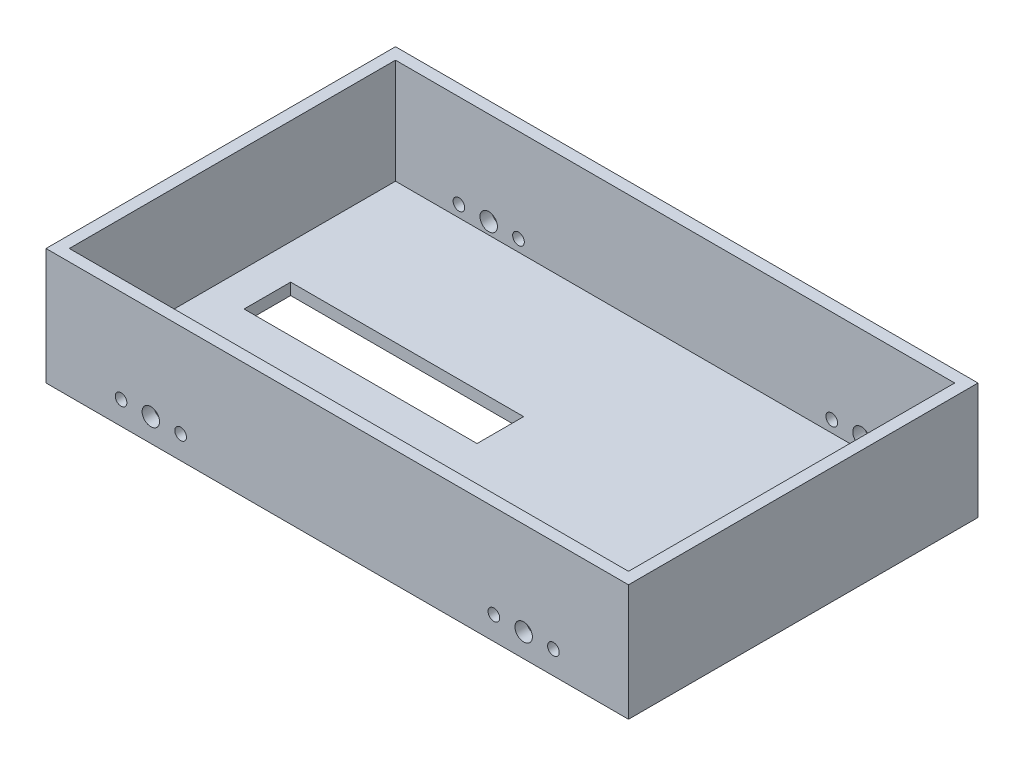
SolidWorks part; units mm, degrees
ref_plane "Front Plane" through (0, 0, 0) normal (0, 0, 1) x (1, 0, 0)
ref_plane "Top Plane" through (0, 0, 0) normal (0, 1, 0) x (1, 0, 0)
ref_plane "Right Plane" through (0, 0, 0) normal (1, 0, 0) x (0, 0, -1)
sketch "Sketch1" plane through (0, 0, 0) normal (0, 1, 0) x (1, 0, 0)
  line L1 (125, -75) -> (-125, -75)
  line L2 (125, -75) -> (125, 75)
  line L3 (125, 75) -> (-125, 75)
  line L4 (-125, -75) -> (-125, 75)
  line L5 (125, -75) -> (-125, 75) construction
  line L6 (125, 75) -> (-125, -75) construction
  point P0 (0, 0)
  dimension "D1" = 150
  dimension "D2" = 250
extrude "Boss-Extrude1" add sketch "Sketch1" along normal blind 50 contours L1 L4 L3 L2
shell "Shell1" thickness 5 removed face at (0, 50, 0)
sketch "Sketch3" plane through (0, 0, 75) normal (0, 0, 1) x (1, 0, 0)
  line L0 (0, -27.5) -> (0, 27.5) construction
  line L1 (-80, 10) -> (-80, 25.1535) construction
  line L2 (0, 0) -> (0, 67.0871) construction
  circle A0 centre (-80, 10) radius 3.75
  circle A1 centre (80, 10) radius 3.75
  circle A2 centre (-92.78, 10) radius 2.5
  circle A4 centre (-67.22, 10) radius 2.5
  circle A5 centre (67.22, 10) radius 2.5
  circle A6 centre (92.78, 10) radius 2.5
  dimension "BushingDiam" = 7.5
  dimension "M5" = 5
  dimension "DistanceFromCenter" = 80
  dimension "HeightWheel" = 10
  dimension "M5Dist" = 12.78
extrude "Cut-Extrude1" cut sketch "Sketch3" against normal up to surface (150 mm away) up to face at (0, 25, -75)
sketch "Sketch4" plane through (0, 5, 0) normal (0, 1, 0) x (1, 0, 0)
  line L0 (-120, -70) -> (-120, 70) construction
  line L1 (-105, 10) -> (-5, 10)
  line L2 (-105, 10) -> (-105, -10)
  line L3 (-105, -10) -> (-5, -10)
  line L4 (-5, 10) -> (-5, -10)
  dimension "D1" = 15
  dimension "GearboxWidth" = 20
  dimension "GearboxLength" = 100
  dimension "D2" = 10
extrude "Cut-Extrude2" cut sketch "Sketch4" against normal through all
